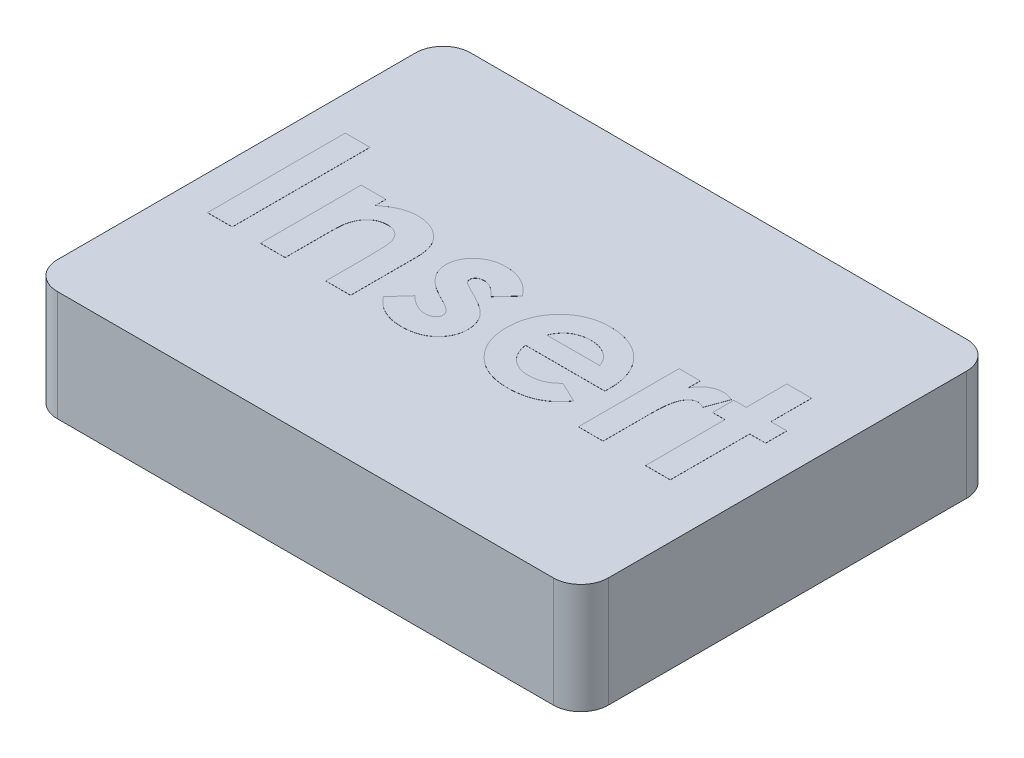
SolidWorks part; units mm, degrees
ref_plane "Front Plane" through (0, 0, 0) normal (0, 0, 1) x (1, 0, 0)
ref_plane "Top Plane" through (0, 0, 0) normal (0, 1, 0) x (1, 0, 0)
ref_plane "Right Plane" through (0, 0, 0) normal (1, 0, 0) x (0, 0, -1)
sketch "Sketch1" plane through (0, 0, 0) normal (0, 1, 0) x (1, 0, 0)
  line L0 (0, 0) -> (12.7, 0)
  line L1 (12.7, 0) -> (12.7, 9.525)
  line L2 (12.7, 9.525) -> (0, 9.525)
  line L3 (0, 9.525) -> (0, 0)
  dimension "D1" = 12.7
  dimension "D2" = 9.525
extrude "Boss-Extrude1" add sketch "Sketch1" along normal blind 2.54
fillet "Fillet1" radius 0.635 4 edges at (0, 1.27, -9.525) (12.7, 1.27, -9.525) (12.7, 1.27, 0) (0, 1.27, 0)
shell "Shell1" thickness 0.635 removed face at (6.35, 0, -4.7625)
sketch "Sketch2" plane through (0, 1.905, 0) normal (0, -1, 0) x (-1, 0, 0)
  line L0 (-0.635, 4.7625) -> (-12.065, 4.7625) construction
  line L1 (-0.635, 8.89) -> (-0.635, 0.635) construction
  line L2 (-12.065, 0.635) -> (-12.065, 8.89) construction
  line L3 (-6.35, 0.635) -> (-6.35, 8.89) construction
  line L4 (-0.635, 0.635) -> (-12.065, 0.635) construction
  line L5 (-12.065, 8.89) -> (-0.635, 8.89) construction
  circle A0 centre (-6.35, 4.7625) radius 2.54
  dimension "D1" = 5.08
extrude "Boss-Extrude2" add sketch "Sketch2" along normal up to surface (1.905 mm away) up to face at (6.35, 0, -4.7625)
sketch "Sketch3" plane through (0, 2.54, 0) normal (0, 1, 0) x (1, 0, 0)
  line L0 (0.635, 0) -> (12.065, 0) construction
  line L1 (0, 8.89) -> (0, 0.635) construction
  text T0 "<b>Insert</b>"
  dimension "D1" = 3.302
  dimension "D2" = 0.508
extrude "Boss-Extrude3" add sketch "Sketch3" along normal blind 0.0025
